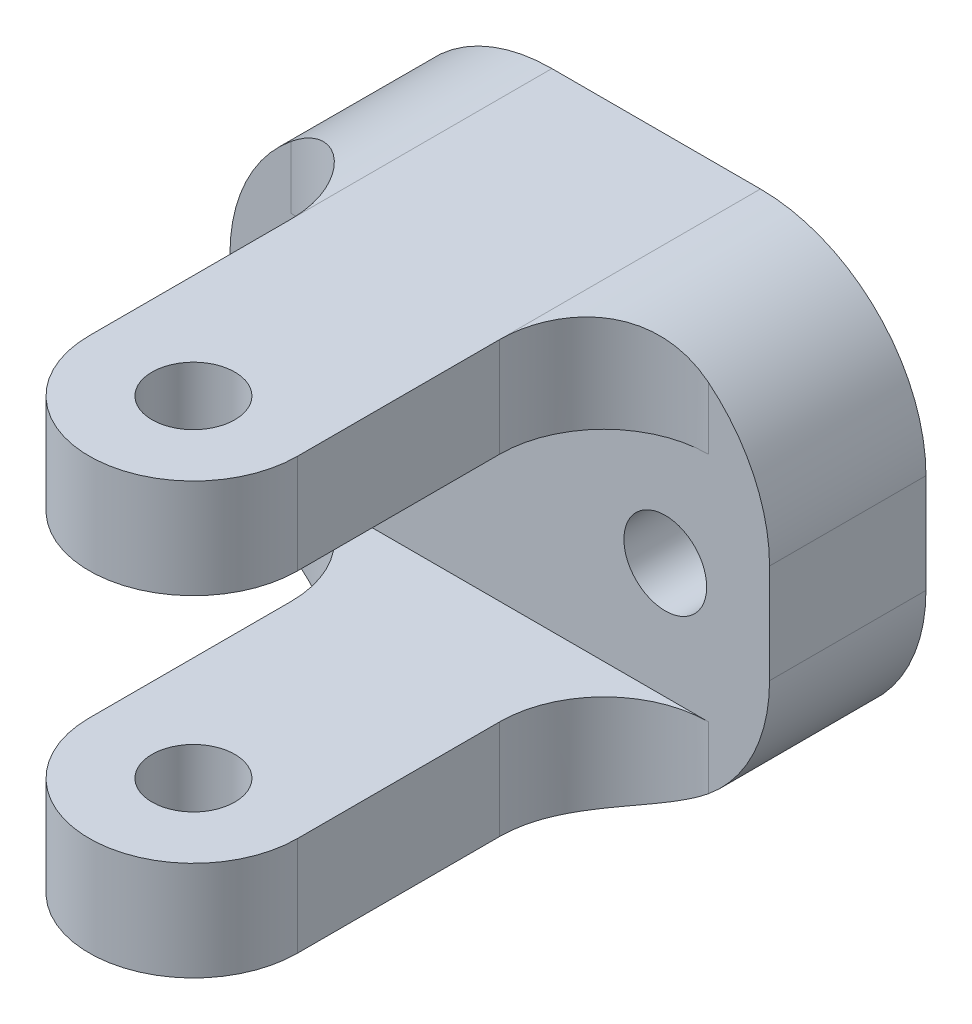
SolidWorks part; units mm, degrees
material "7075-T6 (SN)"
ref_plane "Front Plane" through (0, 0, 0) normal (0, 0, 1) x (1, 0, 0)
ref_plane "Top Plane" through (0, 0, 0) normal (0, 1, 0) x (1, 0, 0)
ref_plane "Right Plane" through (0, 0, 0) normal (1, 0, 0) x (0, 0, -1)
sketch "Sketch1" plane through (0, 0, 0) normal (0, 0, 1) x (1, 0, 0)
  line L0 (12.7, 0) -> (-12.7, 0) construction
  line L1 (-20.7, -16.51) -> (20.7, -16.51)
  line L2 (-20.7, -16.51) -> (-20.7, 16.51)
  line L3 (-20.7, 16.51) -> (20.7, 16.51)
  line L4 (20.7, -16.51) -> (20.7, 16.51)
  line L5 (-20.7, -16.51) -> (20.7, 16.51) construction
  line L6 (-20.7, 16.51) -> (20.7, -16.51) construction
  circle A0 centre (12.7, 0) radius 3.175
  circle A1 centre (-12.7, 0) radius 3.175
  point P0 (0, 0)
  dimension "D1" = 6.35
  dimension "D2" = 25.4
  dimension "D3" = 8
  dimension "D4" = 16.51
extrude "Boss-Extrude1" add sketch "Sketch1" along normal blind 12
sketch "Sketch2" plane through (0, 0, 12) normal (0, 0, 1) x (1, 0, 0)
  line L0 (-12.7, 0) -> (12.7, 0) construction
  line L2 (-20.7, 8.89) -> (20.7, 8.89)
  line L3 (-20.7, 8.89) -> (-20.7, 16.51)
  line L4 (-20.7, 16.51) -> (20.7, 16.51)
  line L5 (20.7, 8.89) -> (20.7, 16.51)
  line L6 (-20.7, 8.89) -> (20.7, 16.51) construction
  line L7 (-20.7, 16.51) -> (20.7, 8.89) construction
  line L8 (-20.7, 16.51) -> (-20.7, -16.51) construction
  line L9 (20.7, -8.89) -> (20.7, -16.51)
  line L10 (-20.7, -8.89) -> (-20.7, -16.51)
  line L11 (-20.7, -16.51) -> (20.7, -8.89) construction
  line L12 (-20.7, -8.89) -> (20.7, -16.51) construction
  line L13 (-20.7, -8.89) -> (20.7, -8.89)
  line L14 (-20.7, -16.51) -> (20.7, -16.51)
  circle A0 centre (-12.7, 0) radius 3.175 construction
  circle A1 centre (12.7, 0) radius 3.175 construction
  point P6 (0, 12.7)
  point P21 (0, -12.7)
  dimension "D1" = 17.78
extrude "Boss-Extrude2" add sketch "Sketch2" along normal blind 53
sketch "Sketch3" plane through (0, 0, 0) normal (0, 1, 0) x (1, 0, 0)
  point P0 (0, -35.5)
  dimension "D1" = 35.5
ref_point "UBJ Point"
sketch "Sketch4" plane through (0, 0, 0) normal (0, 1, 0) x (1, 0, 0)
  circle A0 centre (0, -35.5) radius 3.175
  dimension "D1" = 6.35
extrude "Cut-Extrude1" cut sketch "Sketch4" against normal up to surface and the other way up to surface up to face at (0, -16.51, 32.5) other way up to face at (0, 16.51, 32.5)
sketch "Sketch5" plane through (0, 0, 0) normal (0, 1, 0) x (1, 0, 0)
  line L0 (20.7, -12) -> (8.3595, -39.2814)
  line L1 (-8.3595, -39.2814) -> (-20.7, -12)
  line L4 (20.7, 0) -> (-20.7, 0)
  line L5 (-20.7, 0) -> (-20.7, -65)
  line L6 (-20.7, -65) -> (20.7, -65)
  line L7 (20.7, -65) -> (20.7, 0)
  line L9 (-20.7, -12) -> (-20.7, -65)
  line L10 (-20.7, -65) -> (20.7, -65)
  line L11 (20.7, -65) -> (20.7, -12)
  line L12 (20.7, -12) -> (-20.7, -12)
  line L13 (20.7, -65) -> (20.7, -12)
  line L14 (-20.7, -65) -> (20.7, -65)
  line L15 (-20.7, -12) -> (-20.7, -65)
  line L17 (20.7, -65) -> (20.7, -12)
  line L18 (-20.7, -65) -> (20.7, -65)
  line L19 (-20.7, -12) -> (-20.7, -65)
  arc A0 (-8.3595, -39.2814) -> (8.3595, -39.2814) centre (0, -35.5) ccw
  circle A1 centre (0, -35.5) radius 3.175 construction
  circle A2 centre (0, -35.5) radius 3.175 construction
  dimension "D3" = 6
  dimension "D1" = 0
  dimension "D2" = 0
extrude "Cut-Extrude2" [suppressed] cut sketch "Sketch5" against normal up to surface and the other way up to surface contours A0 L1 L9 L10 L11 L0 up to face at (0, -16.51, 38.675) other way up to face at (0, 16.51, 32.325)
sketch "Sketch6" plane through (0, 0, 0) normal (0, 1, 0) x (1, 0, 0)
  line L0 (-8, -35.5) -> (-8, -20)
  line L1 (8, -35.5) -> (8, -20)
  line L2 (-16, -12) -> (-20.7, -12)
  line L4 (20.7, -12) -> (-20.7, -12)
  line L5 (-20.7, -12) -> (-20.7, -65)
  line L6 (-20.7, -65) -> (20.7, -65)
  line L7 (20.7, -65) -> (20.7, -12)
  line L8 (20.7, -12) -> (16, -12)
  line L9 (-20.7, -12) -> (-20.7, -65)
  line L10 (-20.7, -65) -> (20.7, -65)
  line L11 (20.7, -65) -> (20.7, -12)
  arc A0 (-8, -35.5) -> (8, -35.5) centre (0, -35.5) ccw
  circle A1 centre (0, -35.5) radius 3.175 construction
  arc A2 (-8, -20) -> (-16, -12) centre (-16, -20) ccw
  arc A3 (8, -20) -> (16, -12) centre (16, -20) cw
  dimension "D2" = 8
  dimension "D3" = 8
  dimension "D1" = 0
extrude "Cut-Extrude3" cut sketch "Sketch6" against normal up to surface and the other way up to surface up to face at (0, -16.51, 38.675) other way up to face at (0, 16.51, 32.325)
fillet "Fillet1" radius 12.7 4 edges at (-20.7, -16.51, 6) (-20.7, 16.51, 6) (20.7, -16.51, 6) (20.7, 16.51, 6)
